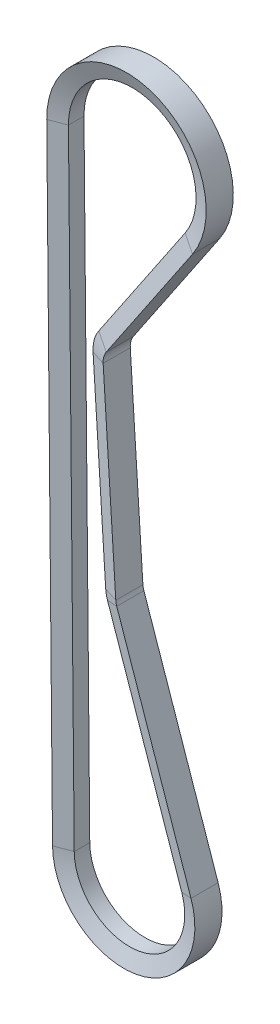
SolidWorks part; units mm, degrees
ref_plane "Front Plane" through (0, 0, 0) normal (0, 0, 1) x (1, 0, 0)
ref_plane "Top Plane" through (0, 0, 0) normal (0, 1, 0) x (1, 0, 0)
ref_plane "Right Plane" through (0, 0, 0) normal (1, 0, 0) x (0, 0, -1)
sketch "Sketch2" plane through (0, 0, 0) normal (0, 0, 1) x (1, 0, 0)
  line L0 (0, 0) -> (1, 0) construction
  line L1 (0, 0) -> (0, 1) construction
  line L9 (24.1761, 204.336) -> (-6.1487, 159.3963)
  line L10 (-7.2222, 155.4417) -> (-2.783, 85.5826)
  line L11 (-2.45, 83.9183) -> (23.6384, 8.1378)
  line L12 (-24.9989, -0.2311) -> (-27.0327, 219.739)
  arc A4 (-27.0327, 219.739) -> (24.1761, 204.336) centre (0.9661, 219.9979) cw
  arc A5 (-6.1487, 159.3963) -> (-7.2222, 155.4417) centre (-0.885, 155.8444) ccw
  arc A6 (-2.783, 85.5826) -> (-2.45, 83.9183) centre (3.5542, 85.9853) ccw
  arc A7 (23.6384, 8.1378) -> (-24.9989, -0.2311) centre (0, 0) cw
ref_plane "Plane4" through (23.6384, 8.1378, 0) normal (0.3255, -0.9455, 0) x (0, 0, -1)
sketch "Sketch3" plane through (23.6384, 8.1378, 0) normal (0.3255, -0.9455, 0) x (0, 0, -1)
  line L0 (-4.7625, 0) -> (4.7625, 0)
  line L1 (-4.7625, 0) -> (-2.7286, -5.588)
  line L2 (-2.7286, -5.588) -> (2.7286, -5.588)
  line L3 (2.7286, -5.588) -> (4.7625, 0)
  line L4 (0, 0) -> (0, -5.588) construction
  dimension "D1" = 9.525
  dimension "D2" = 5.588
  dimension "D3" = 40
sweep "Sweep1" add profiles "Sketch3" path "Sketch2"
